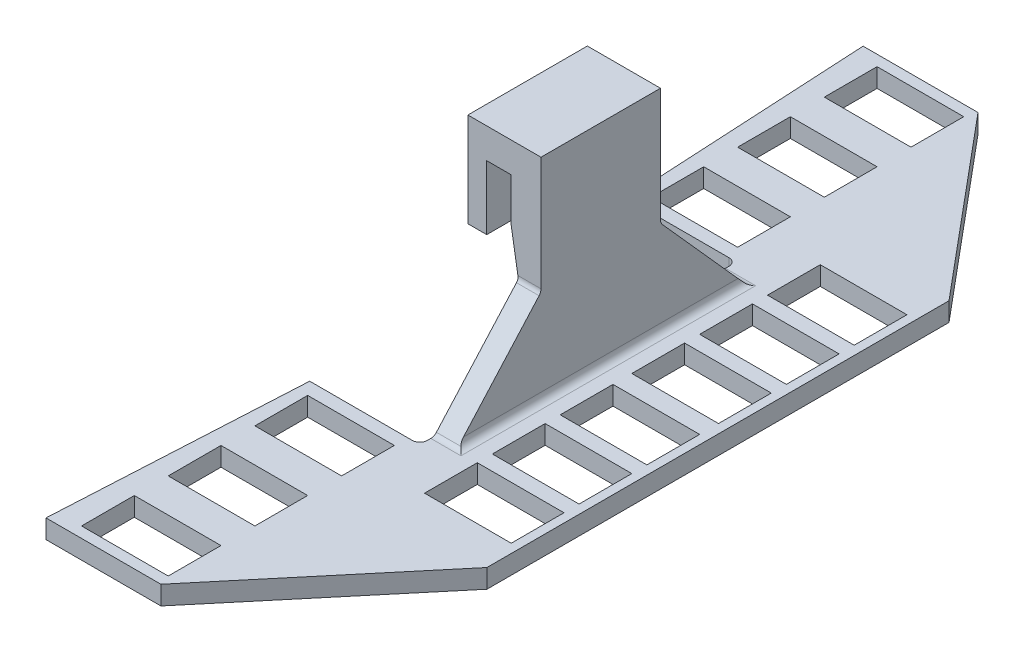
SolidWorks part; units mm, degrees
ref_plane "Plano frontal" through (0, 0, 0) normal (0, 0, 1) x (1, 0, 0)
ref_plane "Plano superior" through (0, 0, 0) normal (0, 1, 0) x (1, 0, 0)
ref_plane "Plano direito" through (0, 0, 0) normal (1, 0, 0) x (0, 0, -1)
sketch "Esboço1" plane through (0, 0, 0) normal (0, 1, 0) x (1, 0, 0)
  line L0 (6, 17.9) -> (8, 17.9) construction
  line L1 (-8, -33) -> (8, -33) construction
  line L2 (-8, -33) -> (-8, 33) construction
  line L3 (-8, 33) -> (8, 33) construction
  line L4 (8, -33) -> (8, 33) construction
  line L5 (-8, -33) -> (8, 33) construction
  line L6 (-8, 33) -> (8, -33) construction
  line L7 (4.5, 19.4) -> (4.5, 33) construction
  line L8 (4.5, -19.6) -> (4.5, -33) construction
  line L9 (4.5, -16.6) -> (8, -16.6)
  line L10 (4.5, -19.6) -> (8, -19.6)
  line L11 (4.5, 16.4) -> (8, 16.4)
  line L12 (4.5, 19.4) -> (8, 19.4)
  line L13 (8, -16.6) -> (8, -14.8)
  line L14 (8, 16.4) -> (8, 15.3)
  line L15 (-8, 33) -> (-8, -33)
  line L16 (-8, -33) -> (8, -33)
  line L17 (8, -33) -> (8, -19.6)
  line L18 (-8, 33) -> (8, 33)
  line L19 (8, 33) -> (8, 19.4)
  line L20 (8, 15.3) -> (1, 15.3)
  line L21 (1, 15.3) -> (1, -14.8)
  line L22 (1, -14.8) -> (8, -14.8)
  line L23 (-8, -33) -> (-24.3938, -54.2)
  line L24 (-24.3938, -54.2) -> (-9.15, -54.2)
  line L26 (-8, 33) -> (-24.3938, 54.2)
  line L27 (-24.3938, 54.2) -> (-9.15, 54.2)
  line L28 (-9.15, 54.2) -> (10.5532, 30.65)
  line L29 (10.5532, 30.65) -> (10.5532, -30.65)
  line L30 (10.5532, -30.65) -> (-9.15, -54.2)
  line L32 (-8, -21) -> (-22.6103, -21)
  line L33 (-22.6103, -21) -> (-24.3938, -54.2)
  line L34 (-8, 21) -> (-22.6103, 21)
  line L35 (-22.6103, 21) -> (-24.3938, 54.2)
  line L36 (0, -55) -> (0, 55) construction
  circle A0 centre (4.5, 17.9) radius 1.5 construction
  circle A1 centre (4.5, -18.1) radius 1.5 construction
  arc A2 (4.5, 19.4) -> (4.5, 16.4) centre (4.5, 17.9) ccw
  arc A3 (4.5, -19.6) -> (4.5, -16.6) centre (4.5, -18.1) cw
  point P0 (0, 0)
  dimension "D3" = 3
  dimension "D4" = 2
  dimension "D1" = 66
  dimension "D2" = 16
  dimension "D5" = 13.6
  dimension "D6" = 13.4
  dimension "D7" = 7
  dimension "D8" = 1.8
  dimension "D9" = 1.1
  dimension "D10" = 12
  dimension "D11" = 54.2
  dimension "D12" = 12
  dimension "D13" = 54.2
  dimension "D14" = 30.65
  dimension "D15" = 30.65
  dimension "D16" = 9.15
extrude "Ressalto-extrusão1" add sketch "Esboço1" along normal blind 2.5 contours A3 L10 L17 L16 L23 L24 L30 L29 L28 L27 L26 L18 L19 L12 A2 L11 L14 L20 L21 L22 L13 L9 | L23 L15 | L35 L34 L15 L26 | L22 L13 L9 A3 L10 L17 L16 L15 L18 L19 L12 A2 L11 L14 L20 L21 region at (6.25, 0, 17.7389) region at (-16.9295, 0, 33.2208) region at (-16.9295, 0, -33.2208)
sketch "Esboço2" plane through (0, 2.5, 0) normal (0, 1, 0) x (1, 0, 0)
  line L0 (8, 33) -> (-8, 33) construction
  line L1 (-8, -33) -> (-5, -33)
  line L2 (-8, -33) -> (-8, 33)
  line L3 (-8, 33) -> (-5, 33)
  line L4 (-5, -33) -> (-5, 33)
  dimension "D1" = 3
extrude "Ressalto-extrusão2" add sketch "Esboço2" along normal blind 12.5
sketch "Esboço4" plane through (0, 0, 0) normal (0, 0, 1) x (1, 0, 0)
  line L0 (-8, 15) -> (-8, 0) construction
  line L1 (-5, 15) -> (-9, 15)
  line L2 (-5, 15) -> (-5, 26.5)
  line L3 (-5, 26.5) -> (-9, 26.5)
  line L4 (-9, 15) -> (-9, 26.5)
  line L6 (-5, 26.5) -> (-14.7, 26.5)
  line L7 (-5, 26.5) -> (-5, 30.5)
  line L8 (-5, 30.5) -> (-14.7, 30.5)
  line L9 (-14.7, 26.5) -> (-14.7, 30.5)
  line L10 (-14.7, 26.5) -> (-12.2, 26.5)
  line L11 (-14.7, 26.5) -> (-14.7, 18)
  line L12 (-14.7, 18) -> (-12.2, 18)
  line L13 (-12.2, 26.5) -> (-12.2, 18)
  dimension "D1" = 1
  dimension "D2" = 11.5
  dimension "D3" = 4
  dimension "D4" = 2.5
  dimension "D5" = 3.2
  dimension "D6" = 3
extrude "Ressalto-extrusão4" add sketch "Esboço4" along normal mid plane 15.85 contours L4 L1 L2 L3 | L9 L6 L3 L7 L8 | L13 L6 L11 L12 region at (-7, 20.75, 0) region at (-9.85, 28.5, 0) region at (-13.45, 22.25, 0)
chamfer "Chanfro1" distance 6 distance2 1 1 edges at (-9, 15, 0) first distance on face at (-9, 20.75, 0)
chamfer "Chanfro2" distance 12 angle 45 2 edges at (-6.5, 15, 33) (-6.5, 15, -33)
sketch "Esboço6" plane through (-5, 0, 0) normal (1, 0, 0) x (0, 0, -1)
  line L0 (-21, 15) -> (-21, 2.5)
  line L1 (-33, 2.5) -> (33, 2.5) construction
  line L2 (-21, 2.5) -> (-33, 2.5)
  line L3 (-33, 2.5) -> (-33, 15)
  line L4 (-33, 15) -> (-21, 15)
  line L5 (21, 15) -> (21, 2.5)
  line L6 (21, 2.5) -> (33, 2.5)
  line L7 (33, 2.5) -> (33, 15)
  line L8 (33, 15) -> (21, 15)
  line L9 (-21, 2.5) -> (-7.92, 15)
  line L10 (-21, 15) -> (-7.925, 15) construction
  line L11 (-7.92, 15) -> (-21, 15)
  line L12 (21, 2.5) -> (9, 15)
  line L13 (7.925, 15) -> (21, 15) construction
  line L14 (9, 15) -> (21, 15)
  line L15 (0, 16.775) -> (0, -16.775) construction
  line L16 (-21, 2.5) -> (-19.1, 2.5)
  line L17 (-19.1, 2.5) -> (-7.92, 15)
  line L18 (21, 2.5) -> (19.1, 2.5)
  line L19 (19.1, 2.5) -> (9, 15)
  line M9 (-7.925, 15) -> (-21, 15)
  line M10 (-21, 15) -> (-33, 3)
  line M11 (-33, 3) -> (-33, 2.5)
  line M12 (-33, 2.5) -> (33, 2.5)
  dimension "D1" = 7.92
  dimension "D2" = 9
  dimension "D3" = 19.1
  dimension "D4" = 19.1
extrude "Corte-extrusão2" cut sketch "Esboço6" against normal up to surface (3 mm away) contours L0 M10 M11 M12 | L0 L9 M9 | L4 L3 M10 | L17 L9 M12 region at (-5, 10.8333, 16.64) region at (-5, 11, 29) region at (-5, 6.6731, 25.1538) region at (-5, 6.6667, 16.0067) up to face at (-8, 6.3333, 0)
sketch "Esboço5" plane through (0, 2.5, 0) normal (0, 1, 0) x (1, 0, 0)
  line L0 (-16.775, 0) -> (16.775, 0) construction
  line L1 (-1.3757, -7.5) -> (8.6243, -7.5) construction
  line L2 (-1.3757, -7.5) -> (-1.3757, -2) construction
  line L3 (-1.3757, -2) -> (8.6243, -2) construction
  line L4 (8.6243, -7.5) -> (8.6243, -2) construction
  line L5 (-2.1257, -8.25) -> (9.3743, -8.25)
  line L6 (-2.1257, -8.25) -> (-2.1257, -1.25)
  line L7 (-2.1257, -1.25) -> (9.3743, -1.25)
  line L8 (9.3743, -8.25) -> (9.3743, -1.25)
  point P8 (9.3743, -4.75)
  point P9 (8.6243, -4.75)
  point P10 (3.6243, -7.5)
  point P11 (3.6243, -8.25)
  dimension "D1" = 10
  dimension "D2" = 5.5
  dimension "D3" = 0.75
  dimension "D4" = 0.75
  dimension "D5" = 8.25
  dimension "D6" = 7.5
extrude "Corte-extrusão1" cut sketch "Esboço5" against normal up to next
pattern_linear "Padrão linear1" count 3 spacing 9 along (0, 0, 1) of "Corte-extrusão1"
sketch "Esboço7" plane through (0, 2.5, 0) normal (0, 1, 0) x (1, 0, 0)
  line L0 (-16.775, 0) -> (16.775, 0) construction
  line L1 (-20.1, -27.65) -> (-8.6, -27.65)
  line L2 (-20.1, -27.65) -> (-20.1, -34.65)
  line L3 (-20.1, -34.65) -> (-8.6, -34.65)
  line L4 (-8.6, -27.65) -> (-8.6, -34.65)
  line L5 (0, -16.775) -> (0, 16.775) construction
  dimension "D1" = 7
  dimension "D2" = 11.5
  dimension "D3" = 27.65
  dimension "D4" = 20.1
extrude "Corte-extrusão3" [suppressed] cut sketch "Esboço7" against normal up to next
pattern_linear "Padrão linear2" [suppressed] count 3 spacing 9 of bodies 109
sketch "Esboço8" plane through (0, 2.5, 0) normal (0, 1, 0) x (1, 0, 0)
  line L0 (-16.775, 0) -> (16.775, 0) construction
  line L1 (-21.11, 22.77) -> (-9.61, 22.77)
  line L2 (-21.11, 22.77) -> (-21.11, 29.77)
  line L3 (-21.11, 29.77) -> (-9.61, 29.77)
  line L4 (-9.61, 22.77) -> (-9.61, 29.77)
  line L5 (0, -16.775) -> (0, 16.775) construction
  dimension "D1" = 11.5
  dimension "D2" = 7
  dimension "D3" = 22.77
  dimension "D4" = 21.11
extrude "Corte-extrusão4" cut sketch "Esboço8" against normal blind 10
pattern_linear "Padrão linear3" count 3 spacing 11.5 along (0, 0, -1) of "Corte-extrusão4"
mirror "Espelhar1" about plane through (0, 0, 0) normal (0, 0, 1) of "Padrão linear3"
mirror "Espelhar2" about plane through (0, 0, 0) normal (0, 0, 1) of "Padrão linear1"
mirror "Espelhar3" about plane through (0, 0, 0) normal (0, 0, 1) of "Corte-extrusão2"
fillet "Filete3" radius 1 7 edges at (-8, 1.25, 21) (-6.5, 2.5, 19.1) (-6.5, 2.5, -19.1) (-8, 1.25, -21) (-5, 2.5, 0) (-6.5, 15, -7.925) (-6.5, 15, 7.925)
fillet "Filete5" radius 1 2 edges at (-6.5, 15, -7.92) (-6.5, 15, 7.92)
